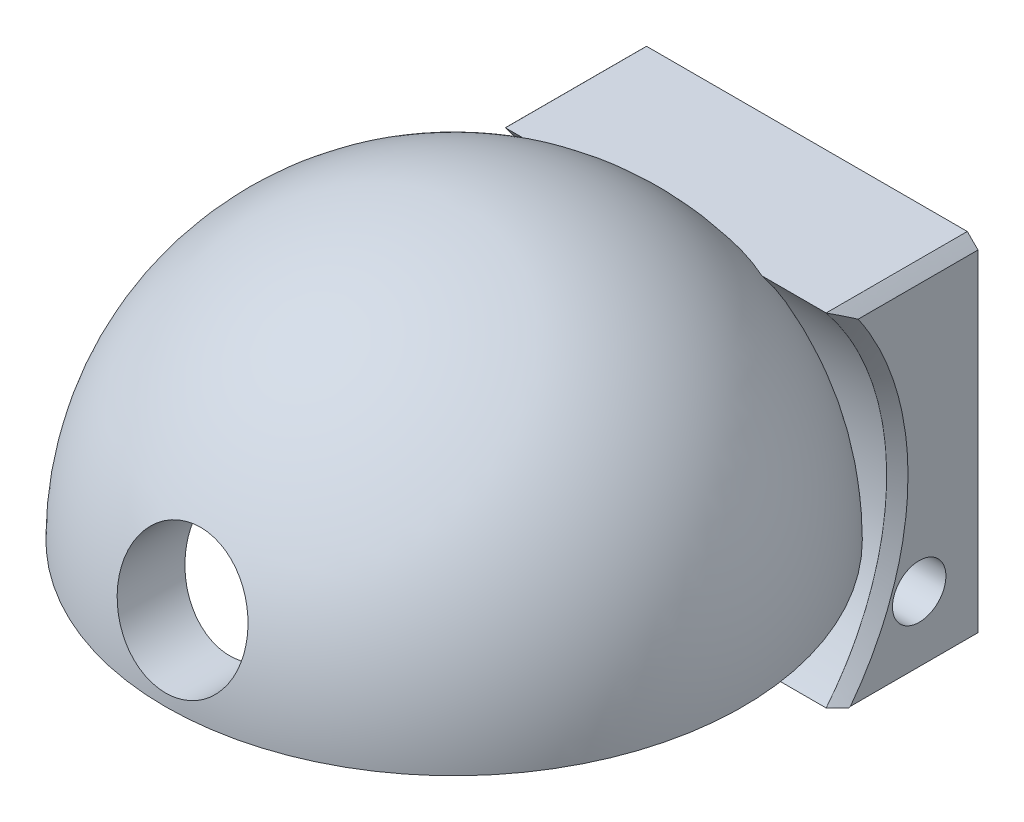
SolidWorks part; units mm, degrees
ref_plane "Front Plane" through (0, 0, 0) normal (0, 0, 1) x (1, 0, 0)
ref_plane "Top Plane" through (0, 0, 0) normal (0, 1, 0) x (1, 0, 0)
ref_plane "Right Plane" through (0, 0, 0) normal (1, 0, 0) x (0, 0, -1)
ref_plane "Plane1" through (-3.25, 0, 0) normal (-1, 0, 0) x (0, 0, 1)
sketch "Sketch2" plane through (-3.25, 0, 0) normal (-1, 0, 0) x (0, 0, 1)
  line L0 (-1.628, 8.4513) -> (-4.628, 8.4513) construction
  line L5 (11.872, 18.9513) -> (11.872, 21.9513)
  line L6 (1.372, 8.4513) -> (-1.628, 8.4513)
  line L7 (11.872, 21.9513) -> (11.872, 8.4513) construction
  arc A0 (11.872, 21.9513) -> (-1.628, 8.4513) centre (11.872, 8.4513) ccw
  arc A3 (11.872, 18.9513) -> (1.372, 8.4513) centre (11.872, 8.4513) ccw
  arc A4 (1.372, 8.4513) -> (5.0713, 0.4513) centre (11.872, 8.4513) ccw construction
  arc A5 (1.372, 8.4513) -> (5.0713, 0.4513) centre (11.872, 8.4513) ccw construction
  dimension "D1" = 3
revolve "Revolve1" add sketch "Sketch2" angle 360 about L7
sketch "Sketch3" plane through (0, 0, -4.628) normal (0, 0, 1) x (1, 0, 0)
  line L0 (-7.75, 8.4513) -> (1.25, 8.4513) construction
  line L1 (-7.75, 8.4513) -> (1.25, 8.4513)
  line L2 (-5.75, 11.9513) -> (-7.75, 11.9513) construction
  line L3 (-3.25, 14.4513) -> (-3.25, 16.4513) construction
  line L4 (-0.75, 11.9513) -> (1.25, 11.9513) construction
  line L5 (-7.75, 8.4513) -> (1.25, 8.4513)
  line L6 (-7.75, 8.4513) -> (-7.75, 16.4513)
  line L7 (-7.75, 16.4513) -> (1.25, 16.4513)
  line L8 (1.25, 8.4513) -> (1.25, 16.4513)
  line L9 (-3.25, 9.4513) -> (-3.25, 8.4513) construction
  circle A0 centre (-3.25, 11.9513) radius 2.5 construction
  circle A2 centre (-3.25, 11.9513) radius 1.25
  circle M11 centre (-3.25, 11.9513) radius 1.25
  dimension "D1" = 2.5
  dimension "D2" = 5
  dimension "D3" = 1
extrude "Boss-Extrude1" add sketch "Sketch3" along normal up to surface (7.0132 mm away) contours L1 L8 L7 L6 M11 region at (-7.6296, 12.4513, -4.628) up to face at (-13.75, 8.4513, 11.872)
ref_plane "5mmHeadPlane" through (0, 0, -1.628) normal (0, 0, -1) x (-1, 0, 0)
sketch "Sketch4" plane through (0, 0, -1.628) normal (0, 0, 1) x (1, 0, 0)
  circle A4 centre (-3.25, 11.9513) radius 2.95
  circle A5 centre (-3.25, 11.9513) radius 2.95
  dimension "D1" = 1.7
extrude "Cut-Extrude1" cut sketch "Sketch4" along normal through all
sketch "Sketch5" plane through (1.25, 0, 0) normal (1, 0, 0) x (0, 0, -1)
  line L1 (4.628, 16.4513) -> (-1.9725, 16.4513)
  line L2 (4.628, 16.4513) -> (4.628, 0.4513)
  line L3 (4.628, 0.4513) -> (-1.9725, 0.4513)
  line L6 (-1.9725, 0.4513) -> (4.628, 0.4513) construction
  arc A0 (0.8559, 8.4513) -> (-1.9725, 16.4513) centre (-11.872, 8.4513) ccw construction
  arc A1 (0.8559, 8.4513) -> (-1.9725, 16.4513) centre (-11.872, 8.4513) ccw
  arc A2 (-1.9725, 0.4513) -> (0.8559, 8.4513) centre (-11.872, 8.4513) ccw construction
  arc A3 (-1.9725, 0.4513) -> (0.8559, 8.4513) centre (-11.872, 8.4513) ccw
extrude "Boss-Extrude2" add sketch "Sketch5" along normal blind 3.5
fillet "Fillet1" radius 0.5 2 edges at (4.75, 16.4513, -1.3278) (4.75, 8.4513, -0.8559) conic radius 50
mirror "Mirror1" about plane through (-3.25, 0, 0) normal (-1, 0, 0) of "Fillet1", "Boss-Extrude2"
sketch "Sketch6" plane through (4.75, 0, 0) normal (1, 0, 0) x (0, 0, -1)
  line L1 (3.128, 3.4967) -> (4.628, 3.4967) construction
  line L3 (4.628, 0.4513) -> (4.628, 15.9513) construction
  line L4 (-0.872, 0.7467) -> (4.628, 0.7467) construction
  line L5 (-0.872, 0.7467) -> (-0.872, 6.2467) construction
  line L6 (-0.872, 6.2467) -> (4.628, 6.2467) construction
  line L7 (4.628, 0.7467) -> (4.628, 6.2467) construction
  line L8 (1.878, 3.4967) -> (-0.872, 3.4967) construction
  line L9 (1.878, 3.4967) -> (1.878, 6.2467) construction
  circle A0 centre (1.878, 3.4967) radius 1.25
  dimension "D1" = 2.5
  dimension "D2" = 1.5
extrude "Cut-Extrude2" cut sketch "Sketch6" against normal through all
equation "\"D1@Sketch6\"=3-.5"
equation "\"D1@Sketch3\"=3-.5"
equation "\"D1@Sketch4\"=1.50mm+.2"
